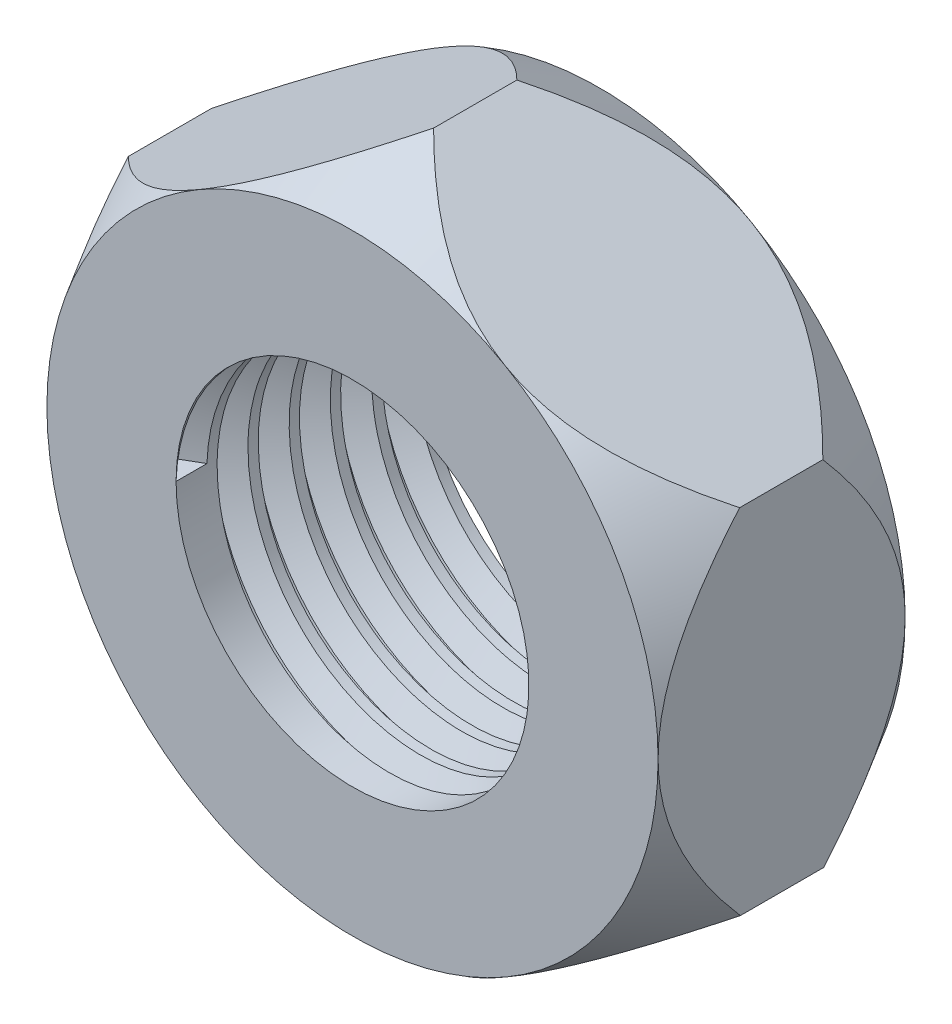
SolidWorks part; units mm, degrees
ref_plane "Front Plane" through (0, 0, 0) normal (0, 0, 1) x (1, 0, 0)
ref_plane "Top Plane" through (0, 0, 0) normal (0, 1, 0) x (1, 0, 0)
ref_plane "Right Plane" through (0, 0, 0) normal (1, 0, 0) x (0, 0, -1)
sketch "Sketch1" plane through (0, 0, 0) normal (0, 0, 1) x (1, 0, 0)
  line L1 (25.9486, 15.0557) -> (-0.0644, 30)
  line L2 (-0.0644, 30) -> (-26.0129, 14.9443)
  line L3 (-26.0129, 14.9443) -> (-25.9486, -15.0557)
  line L4 (-25.9486, -15.0557) -> (0.0644, -30)
  line L5 (0.0644, -30) -> (26.0129, -14.9443)
  line L6 (26.0129, -14.9443) -> (25.9486, 15.0557)
  circle A0 centre (0, 0) radius 25.9808 construction
  dimension "D1" = 60
extrude "Boss-Extrude1" add sketch "Sketch1" along normal blind 21
sketch "Sketch2" plane through (0, 0, 21) normal (0, 0, 1) x (1, 0, 0)
  circle A1 centre (0, 0) radius 25.9808
extrude "Cut-Extrude3" cut sketch "Sketch2" against normal blind 21 draft 30 flip side to cut
sketch "Sketch3" plane through (0, 0, 0) normal (0, 0, -1) x (-1, 0, 0)
  circle A0 centre (0, 0) radius 25.9808
extrude "Cut-Extrude4" cut sketch "Sketch3" against normal blind 21 draft 30 flip side to cut
sketch "Sketch4" plane through (0, 0, 21) normal (0, 0, 1) x (1, 0, 0)
  circle A0 centre (0, 0) radius 15
  dimension "D1" = 30
extrude "Cut-Extrude5" cut sketch "Sketch4" against normal through all
thread "Thread2" pitch 3.5 method cut profile "Thread Profile2" start angle 0, offset 0, length 0, pitch 3.5, diameter 30
ref_plane "Plane2" through (-15, 0, 21) normal (0, -1, 0) x (-1, 0, 0)
sketch "Thread Profile2" plane through (-15, 0, 21) normal (0, -1, 0) x (-1, 0, 0)
  line L0 (0, 0) -> (0, 3.5) construction
  line L1 (0, 0) -> (1.8944, 1.0937)
  line L2 (1.8944, 1.0937) -> (1.8944, 1.5312)
  line L3 (1.8944, 1.5312) -> (0, 2.625)
  line L4 (1.8944, 1.3125) -> (0, 1.3125) construction
  line L11 (0, 0) -> (0, 2.625)
  point P2 (0, 0)
  dimension "Pitch" = 3.5
  dimension "Profile_Angle" = 60
  dimension "Profile_Land" = 0.4375
  dimension "Profile_Height" = 1.8944
